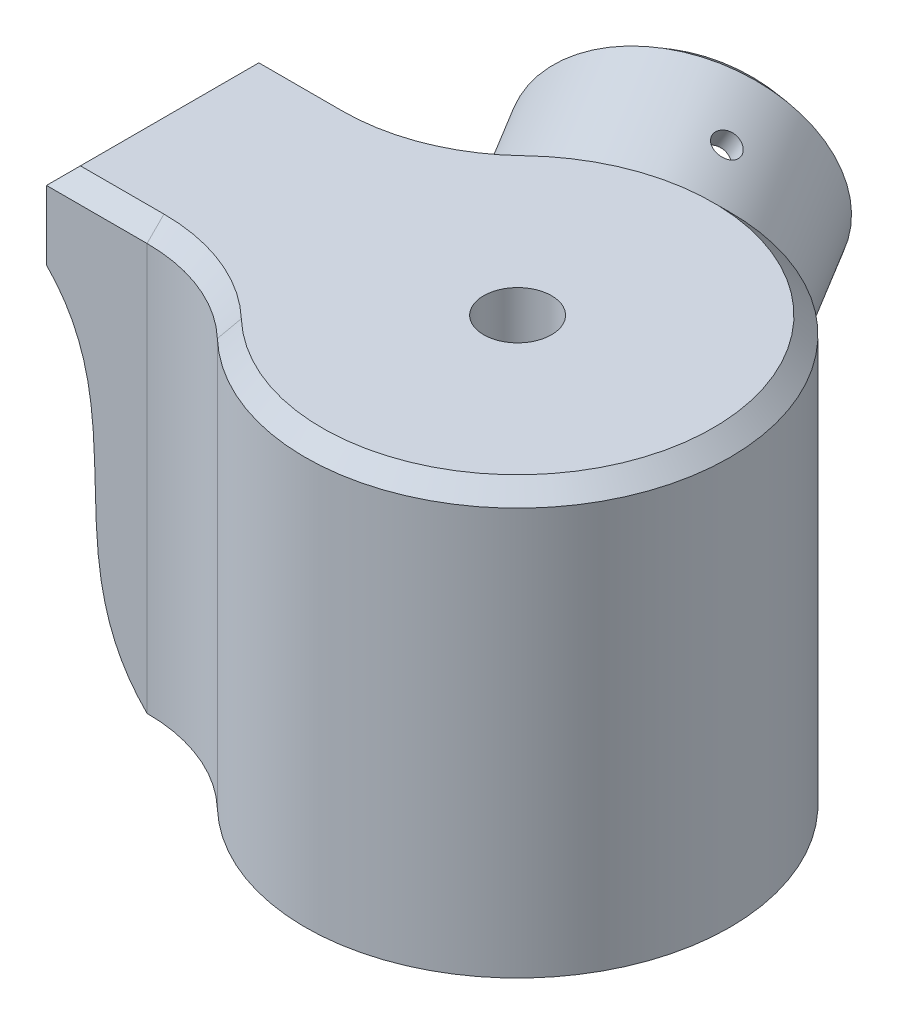
SolidWorks part; units mm, degrees
material "Melamine resin"
ref_plane "Front Plane" through (0, 0, 0) normal (0, 0, 1) x (1, 0, 0)
ref_plane "Top Plane" through (0, 0, 0) normal (0, 1, 0) x (1, 0, 0)
ref_plane "Right Plane" through (0, 0, 0) normal (1, 0, 0) x (0, 0, -1)
sketch "Sketch1" plane through (0, 0, 0) normal (0, 1, 0) x (1, 0, 0)
  line L0 (-37, -12.5248) -> (-25.1408, -12.5248)
  line L1 (-37, -12.5248) -> (-37, 12.5248)
  line L2 (-37, 12.5248) -> (-25.1408, 12.5248)
  arc A0 (-11.2801, -18.0914) -> (-25.1408, -12.5248) centre (-25.1408, -32.5646) ccw
  arc A1 (-25.1408, 12.5248) -> (-11.2801, 18.0914) centre (-25.1408, 32.5646) ccw
  arc A2 (-11.2801, -18.0914) -> (-11.2801, 18.0914) centre (6.0458, 0) ccw
  dimension "D2" = 20.0397
  dimension "D3" = 25.0497
  dimension "D1" = 37
  dimension "D4" = 6.0458
extrude "Boss-Extrude2" add sketch "Sketch1" along normal blind 50
ref_axis "Axis1" through (6.0458, 50, 0) along (0, -1, 0)
ref_point "Point1"
ref_plane "Plane1" through (0, 25, 0) normal (0, 1, 0) x (1, 0, 0)
sketch "Sketch2" plane through (0, 25, 0) normal (0, 1, 0) x (1, 0, 0)
  point P0 (6.0458, 0)
sketch3d "3DSketch2"
  line L0 (6.0458, 25, 0) -> (-125.4586, 70.8173, -246.2467)
chamfer "Chamfer1" distance 2 angle 45 5 edges at (-17.6724, 50, 13.9685) (-17.6724, 50, -13.9685) (31.0955, 50, 0) (-31.0704, 50, 12.5248) (-31.0704, 50, -12.5248)
sketch3d "3DSketch1"
  line L0 (6.0458, 25, 0) -> (-9.6875, 5.6459, 90)
  line L1 (6.0338, 25, 0) -> (-25.4087, -13.7083, 180) construction
ref_plane "Plane2" through (6.0458, 25, 0) normal (-0.4649, 0.162, -0.8705) x (-0.8854, -0.0758, 0.4587)
sketch "Sketch3" plane through (6.0458, 25, 0) normal (-0.4649, 0.162, -0.8705) x (-0.8854, -0.0758, 0.4587)
  circle A0 centre (0, 0) radius 15
  dimension "D1" = 30
extrude "Boss-Extrude3" add sketch "Sketch3" along normal blind 50
sketch "Sketch5" plane through (-23.8183, 8.2985, -44.6006) normal (-0.4649, 0.162, -0.8705) x (-0.8767, -0.2212, 0.4271)
  circle A0 centre (-10.8312, 23.296) radius 12.7
  dimension "D1" = 25.4
extrude "Cut-Extrude1" cut sketch "Sketch5" against normal blind 21
fillet "Fillet2" radius 3 2 edges at (-16.6363, 28.2884, -10.6306) (-17.5453, 23.9713, -14.02)
chamfer "Chamfer2" distance 3 angle 45 1 edges at (-30.4282, 33.0979, -36.4564)
ref_plane "Plane3" through (-37, 48, -12.5248) normal (0.4917, 0.8648, -0.1017) x (0.8707, -0.4872, 0.0669)
sketch "Sketch6" plane through (-37, 48, -12.5248) normal (0.4917, 0.8648, -0.1017) x (0.8707, -0.4872, 0.0669)
  line L0 (24.0545, 30.2209) -> (44.8977, -2.1034) construction
  line L1 (36.6609, 38.3497) -> (11.448, 22.092) construction
  line L2 (49.5248, -9.2792) -> (-103.7829, 228.4745) construction
  circle A0 centre (28.3898, 23.4975) radius 1.5
  dimension "D1" = 3
  dimension "D2" = 8
extrude "Cut-Extrude2" cut sketch "Sketch6" against normal mid plane 40
ref_point "Point2"
sketch "Sketch7" plane through (0, 0, 0) normal (0, -1, 0) x (-1, 0, 0)
  circle A0 centre (-6.0458, 0) radius 4
  dimension "D1" = 8
extrude "Cut-Extrude3" cut sketch "Sketch7" against normal blind 117
sketch "Sketch8" plane through (0, 0, 0) normal (0, -1, 0) x (1, 0, 0)
  circle A0 centre (6.0458, 0) radius 11
  dimension "D1" = 22
extrude "Cut-Extrude4" cut sketch "Sketch8" against normal blind 8
sketch "Sketch9" plane through (0, 0, -12.5248) normal (0, 0, -1) x (-1, 0, 0)
  line L0 (37, 48) -> (37, 0) construction
  line L1 (25.1408, 0) -> (37, 0)
  line L2 (37, 0) -> (37, 39.8592)
  line L3 (37, 48) -> (25.1408, 48) construction
  spline S0 degree 3 poles (25.1408, 0) (36.5072, 11.2641) (26.1211, 28.9323) (37, 39.8592) knots 0 0 0 0 1 1 1 1
  dimension "D1" = 4.2177
  dimension "D2" = 6.1294
  dimension "D3" = 8.1408
  dimension "D4" = 15.0833
  dimension "D5" = 34.9044
extrude "Cut-Extrude5" cut sketch "Sketch9" against normal blind 96
chamfer "Chamfer3" distance 2 angle 45 1 edges at (-37, 50, 0)
